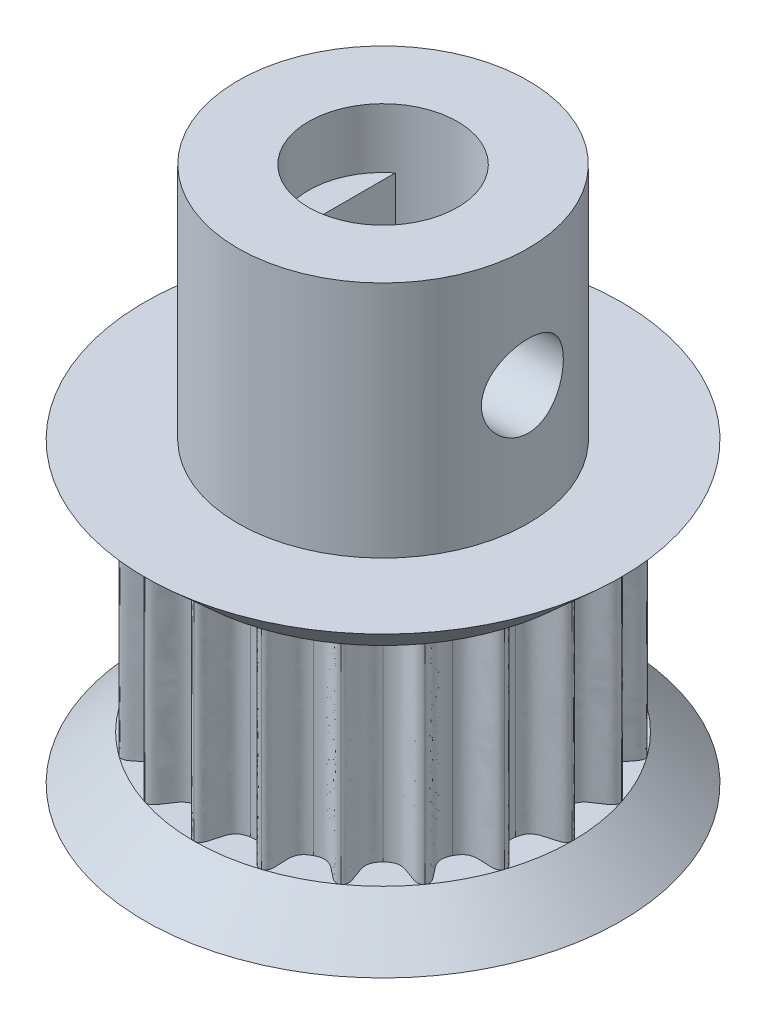
SolidWorks part; units mm, degrees
ref_plane "Front Plane" through (0, 0, 0) normal (0, 0, 1) x (1, 0, 0)
ref_plane "Top Plane" through (0, 0, 0) normal (0, 1, 0) x (1, 0, 0)
ref_plane "Right Plane" through (0, 0, 0) normal (1, 0, 0) x (0, 0, -1)
sketch "Sketch2" plane through (0, 0, 0) normal (0, 1, 0) x (1, 0, 0)
  line L0 (0, 0) -> (0, 6.35) construction
  line L1 (0, 0) -> (-0.9934, 6.2718) construction
  line L2 (0, 0) -> (0.9934, 6.2718) construction
  circle A0 centre (0, 0) radius 6.35 construction
  circle A1 centre (0, 0) radius 5.35
  spline S0 degree 3 poles (0, 6.35) (0.1623, 6.35) (0.3547, 5.7831) (0.3803, 5.3565) (0.8369, 5.2841) knots 0 0 0 0 0.284346 1 1 1 1
  spline S1 degree 3 poles (0, 6.35) (-0.1623, 6.35) (-0.3547, 5.7831) (-0.3803, 5.3565) (-0.8369, 5.2841) knots 0 0 0 0 0.284346 1 1 1 1
  spline S3 degree 2 poles (1.885, 5.8014) (2.0025, 6.0284) (2.0339, 6.0155) knots 0 0 0 0.046399 0.046399 0.046399
  spline S4 degree 2 poles (3.5855, 4.935) (3.7001, 5.1635) (3.6711, 5.1812) knots 0 0 0 0.046399 0.046399 0.046399
  spline S23 degree 2 poles (-1.885, -5.8014) (-2.0025, -6.0284) (-2.0339, -6.0155) knots 0 0 0 0.046399 0.046399 0.046399
  point P14 (0.2623, 6.0291)
  point P148 (0, 0)
  dimension "D1" = 12.7
  dimension "D3" = 1
  dimension "D2" = 9
extrude "Boss-Extrude3" add sketch "Sketch2" along normal mid plane 7 contours A1 | S0 S1 A1 region at (0, 0, 0) region at (0, 0, -5.7338)
sketch "Sketch3" plane through (0, -3.5, 0) normal (0, -1, 0) x (1, 0, 0)
  circle A0 centre (0, 0) radius 6.35
ref_axis "Axis1" through (0, -3.85, 0) along (0, 1, 0)
pattern_circular "CirPattern1" count 20 over 360 about axis through (0, -3.85, 0) along (0, 1, 0) of "Boss-Extrude3"
ref_plane "Plane1" through (0, -5, 0) normal (0, -1, 0) x (-1, 0, 0)
sketch "Sketch4" plane through (0, -5, 0) normal (0, -1, 0) x (-1, 0, 0)
  circle A0 centre (0, 0) radius 8
  dimension "D1" = 16
loft "Loft1" add profiles "Sketch4", "Sketch3" connector at (7.7859, -5, -1.8382) connector at (6.2014, -3.5, -1.3657)
mirror "Mirror1" about plane through (0, 0, 0) normal (0, 1, 0) of bodies 104
combine bodies "Combine1" operation type add bodies to combine 104 110 105
sketch "Sketch5" plane through (0, 5, 0) normal (0, 1, 0) x (1, 0, 0)
  line L0 (0, 2.5) -> (0, -2.5) construction
  line L1 (1.55, 1.9615) -> (1.55, -1.9615)
  line L2 (-1.55, 1.9615) -> (-1.55, -1.9615)
  circle A0 centre (0, 0) radius 2.5
  circle A1 centre (0, 0) radius 4.875
  dimension "D1" = 5
  dimension "D2" = 9.75
  dimension "D3" = 3.1
extrude "Boss-Extrude4" add sketch "Sketch5" along normal blind 8 contours A1 A0 | L2 A0 | L1 A0 region at (1.937, 5, 0) region at (-1.937, 5, 0) region at (-4.7371, 5, 0)
sketch "Sketch6" plane through (-1.55, 0, 0) normal (1, 0, 0) x (0, 0, -1)
  line L0 (0, 5) -> (0, 13) construction
  line L1 (8, 5) -> (-8, 5) construction
  line L2 (4.875, 13) -> (-4.875, 13) construction
  circle A0 centre (0, 9) radius 1.375
  dimension "D1" = 2.75
extrude "Cut-Extrude1" cut sketch "Sketch6" along normal up to surface (6.2271 mm away) up to face at (0, 13, 4.875)
sketch "Sketch7" plane through (0, 13, 0) normal (0, 1, 0) x (1, 0, 0)
  circle A0 centre (0, 0) radius 2.5
  arc A1 (1.55, 1.9615) -> (-1.55, 1.9615) centre (0, 0) ccw construction
extrude "Cut-Extrude2" cut sketch "Sketch7" against normal blind 2
